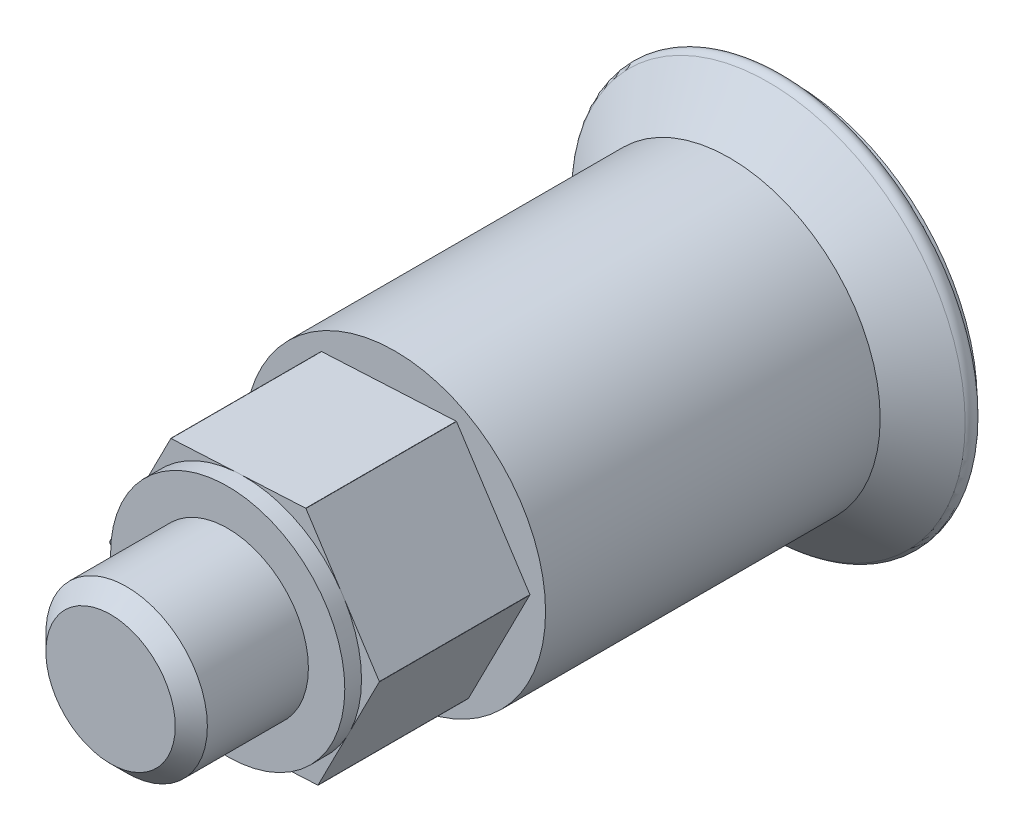
SolidWorks part; units mm, degrees
ref_plane "정면" through (0, 0, 0) normal (0, 0, 1) x (1, 0, 0)
ref_plane "윗면" through (0, 0, 0) normal (0, 1, 0) x (1, 0, 0)
ref_plane "우측면" through (0, 0, 0) normal (1, 0, 0) x (0, 0, -1)
sketch "스케치1" plane through (0, 0, 0) normal (0, 0, 1) x (1, 0, 0)
  circle A1 centre (0, 0) radius 4.5
extrude "보스-돌출1" add sketch "스케치1" along normal blind 10
extrude "보스-돌출2" add sketch "스케치1<2>" against normal blind 1.6 draft 50 draft outward yes
sketch "스케치1<2>" plane through (0, 0, 0) normal (0, 0, 1) x (1, 0, 0) same geometry as "스케치1"
fillet "필렛1" radius 0.25 1 edges at (6.4068, 0, -1.6)
sketch "스케치5" plane through (0, 0, -1.6) normal (0, 0, -1) x (-1, 0, 0)
  circle A0 centre (0, 0) radius 5.5
extrude "보스-돌출3" add sketch "스케치5" along normal blind 0.3
sketch "스케치7" plane through (0, 0, 10) normal (0, 0, 1) x (1, 0, 0)
  line L0 (0, 0) -> (-2.2011, 3.3889)
  line L1 (-2.2011, 3.3889) -> (1.8399, 3.5978)
  line L2 (1.8399, 3.5978) -> (0, 0)
  dimension "D1" = 4.041
  dimension "D2" = 4.041
  dimension "D3" = 4.041
extrude "보스-돌출4" add sketch "스케치7" along normal blind 4.5
pattern_circular "원형 패턴1" count 6 over 360 about axis through (0, 0, 10) along (0, 0, 1) of "보스-돌출4"
sketch "스케치8" plane through (0, 0, 14.5) normal (0, 0, 1) x (1, 0, 0)
  circle A0 centre (0, 0) radius 3.5
extrude "보스-돌출5" add sketch "스케치8" along normal blind 0.5
sketch "스케치9" plane through (0, 0, 15) normal (0, 0, 1) x (1, 0, 0)
  circle A0 centre (0, 0) radius 2.413
  dimension "D1" = 4.826
extrude "보스-돌출6" add sketch "스케치9" along normal blind 3.5
chamfer "모따기1" distance 0.48 angle 45 1 edges at (2.413, 0, 18.5)
ref_point "점1"
